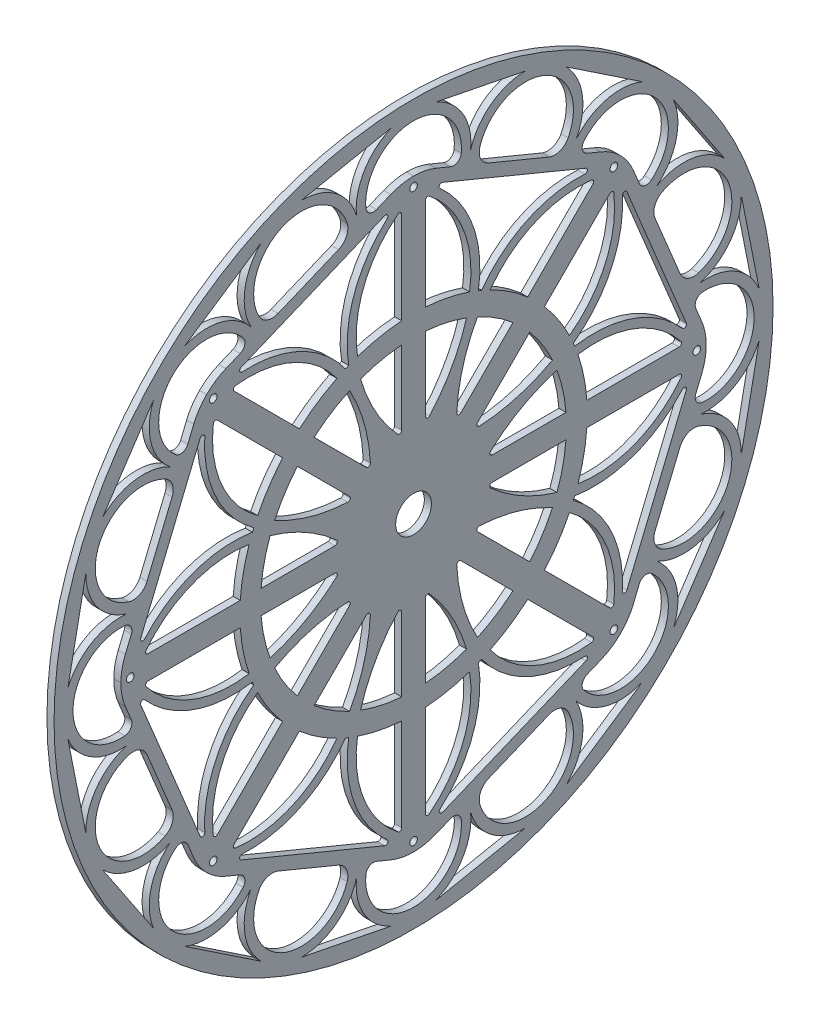
SolidWorks part; units mm, degrees
ref_plane "Front Plane" through (0, 0, 0) normal (1, 0, 0) x (0, 1, 0)
ref_plane "Top Plane" through (0, 0, 0) normal (0, 0, 1) x (0, 1, 0)
ref_plane "Right Plane" through (0, 0, 0) normal (0, 1, 0) x (-1, 0, 0)
sketch "Sketch1" plane through (0, 0, 0) normal (1, 0, 0) x (0, 1, 0)
  line L0 (0, 117.5907) -> (0, 0) construction
  line L1 (83.1492, 83.1492) -> (0, 117.5907) construction
  line L2 (0, 117.5907) -> (-83.1492, 83.1492) construction
  line L4 (-117.5907, 0) -> (-83.1492, -83.1492) construction
  line L5 (-83.1492, -83.1492) -> (0, -117.5907) construction
  line L6 (0, -117.5907) -> (83.1492, -83.1492) construction
  line L7 (83.1492, -83.1492) -> (117.5907, 0) construction
  line L8 (117.5907, 0) -> (83.1492, 83.1492) construction
  line L9 (-83.1492, 83.1492) -> (0, 0) construction
  line L10 (0, 0) -> (-117.5907, 0) construction
  line L11 (-117.5907, 0) -> (-118.1201, 0) construction
  line L12 (-123.5907, 0) -> (-123.5907, 5) construction
  line L14 (-36.2329, 29.1619) -> (-51.4539, 44.3828) construction
  line L15 (-90.9273, 83.8563) -> (-87.3918, 87.3918) construction
  line L16 (-87.3918, 87.3918) -> (-85.6448, 85.6448) construction
  line L18 (-121.1201, 0) -> (-123.5907, 0) construction
  line L19 (-123.5907, 5) -> (-90.9273, 83.8563) construction
  line L20 (-87.1005, 80.0294) -> (-118.1787, 5) construction
  line L21 (-55.2807, 48.2096) -> (-62.699, 30.3003) construction
  line L22 (-59.6103, 24.6914) -> (-36.2329, 29.1619) construction
  line L23 (-67.7667, 5) -> (-51.4539, 44.3828) construction
  line L24 (-59.6103, 24.6914) -> (-46.2411, 5) construction
  line L25 (0, 0) -> (-83.5235, 83.5235)
  line L26 (-55.2807, 48.2096) -> (-84.2721, 77.201) construction
  line L27 (-67.7667, 5) -> (-46.2411, 5) construction
  line L28 (-114.1787, 5) -> (-73.1787, 5) construction
  line L29 (-65.7604, 22.9093) -> (-73.1787, 5) construction
  line L30 (-85.6448, 85.6448) -> (-87.3918, 87.3918)
  line L31 (-83.1492, 83.1492) -> (-88.2348, 70.8713) construction
  line L32 (-87.3918, 87.3918) -> (-90.9273, 83.8563)
  line L33 (-90.9273, 83.8563) -> (-123.5907, 5)
  line L34 (-123.5907, 5) -> (-123.5907, 0)
  line L35 (-123.5907, 0) -> (-121.1201, 0)
  line L36 (-118.1201, 0) -> (0, 0)
  arc A0 (-108.6396, 0) -> (-76.8198, 76.8198) centre (0, 0) ccw construction
  arc A5 (-87.1005, 80.0294) -> (-64.2297, 26.6048) centre (-38.2585, 69.3307) ccw construction
  arc A6 (-114.1787, 5) -> (-65.7604, 22.9093) centre (-76.7606, -21.7561) cw construction
  arc A7 (-84.2721, 77.201) -> (-62.699, 30.3003) centre (-38.8941, 69.6618) ccw construction
  arc A8 (-118.1787, 5) -> (-64.2297, 26.6048) centre (-76.0771, -21.9713) cw construction
  arc A9 (-117.5907, 0) -> (-83.1492, 83.1492) centre (0, 0) ccw construction
  arc A12 (-85.6448, 85.6448) -> (-83.5235, 83.5235) centre (-84.5842, 84.5842) ccw
  arc A13 (-121.1201, 0) -> (-118.1201, 0) centre (-119.6201, 0) cw
  dimension "D1" = 6
  dimension "D8" = 50
  dimension "D9" = 4
  dimension "D12" = 46
  dimension "D13" = 4
  dimension "D4" = 1.5
  dimension "D11" = 1.5
  dimension "D2" = 90
  dimension "D3" = 5
  dimension "D5" = 5
  dimension "D7" = 5
  dimension "D10" = 45
extrude "Boss-Extrude3" add sketch "Sketch1" along normal blind 3
sketch "Sketch2" plane through (3, 0, 0) normal (1, 0, 0) x (0, 1, 0)
  line L0 (-84.2721, 77.201) -> (-55.2807, 48.2096)
  line L1 (-55.2807, 48.2096) -> (-62.699, 30.3003)
  line L2 (-65.7604, 22.9093) -> (-73.1787, 5)
  line L3 (-73.1787, 5) -> (-114.1787, 5)
  line L4 (-118.1787, 5) -> (-87.1005, 80.0294)
  arc A0 (-87.1005, 80.0294) -> (-64.2297, 26.6048) centre (-38.2585, 69.3307) ccw
  arc A1 (-62.699, 30.3003) -> (-84.2721, 77.201) centre (-38.8941, 69.6618) cw
  arc A2 (-64.2297, 26.6048) -> (-118.1787, 5) centre (-76.0771, -21.9713) ccw
  arc A3 (-65.7604, 22.9093) -> (-114.1787, 5) centre (-76.7606, -21.7561) ccw
extrude "Cut-Extrude5" cut sketch "Sketch2" against normal blind 3 contours A2 A0 L4 | A1 L1 L0 | L2 A3 L3 region at (3, -71.2812, 52.1242) region at (3, -87.2608, 13.5461) region at (3, -92.9106, 38.4849)
sketch "Sketch4" plane through (3, 0, 0) normal (1, 0, 0) x (0, 1, 0)
  line L0 (0, 0) -> (-83.5235, 83.5235) construction
  line L1 (-67.7667, 5) -> (-51.4539, 44.3828) construction
  line L2 (-118.1201, 0) -> (0, 0) construction
  line L3 (-58.6536, 27.0011) -> (-60.567, 22.3817) construction
  line L5 (-51.4539, 44.3828) -> (-25.2262, 18.1552)
  line L6 (-67.7667, 5) -> (-30.6753, 5)
  line L7 (-51.4539, 44.3828) -> (-58.6536, 27.0011)
  line L8 (-67.7667, 5) -> (-60.567, 22.3817)
  line L9 (-64.2297, 26.6048) -> (-59.6103, 24.6914) construction
  arc A0 (-18.3848, 18.3848) -> (-58.6536, 27.0011) centre (-24.2, 89.6145) cw construction
  arc A1 (-26, 0) -> (-60.567, 22.3817) centre (-80.479, -46.255) ccw construction
  arc A2 (-25.2262, 18.1552) -> (-58.6536, 27.0011) centre (-24.2, 89.6145) cw
  arc A3 (-60.567, 22.3817) -> (-30.6753, 5) centre (-80.479, -46.255) cw
  dimension "D1" = 26
  dimension "D2" = 26
  dimension "D3" = 5
  dimension "D4" = 5
extrude "Cut-Extrude6" cut sketch "Sketch4" against normal up to vertex (3 mm away) contours A2 L7 L5 | A3 L6 L8 up to point (0, -46.2411, 5)
fillet "Fillet3" radius 1 6 edges at (1.5, -118.1787, 5) (1.5, -87.1005, 80.0294) (1.5, -30.6753, 5) (1.5, -25.2262, 18.1552) (1.5, -114.1787, 5) (1.5, -84.2721, 77.201)
fillet "Fillet4" radius 25 2 edges at (1.5, -90.9273, 83.8563) (1.5, -123.5907, 5)
pattern_circular "CirPattern2" count 8 over 360 about axis through (3, 0, 0) along (-1, 0, 0) of "Boss-Extrude3", "Cut-Extrude5", "Cut-Extrude6", "Fillet3", "Fillet4"
sketch "Sketch5" plane through (3, 0, 0) normal (1, 0, 0) x (0, 0, -1)
  line L0 (0.0272, -123.5907) -> (0, -146.4823)
  line L1 (0, -146.4823) -> (0, -151.7532)
  line L2 (-87.411, -87.3726) -> (-103.6014, -103.5559)
  line L3 (-103.6014, -103.5559) -> (-107.3293, -107.2821)
  line L4 (-83.8563, -90.9273) -> (-5, -123.5907) construction
  line L5 (-62.7141, -99.6847) -> (-44.4281, -107.259) construction
  line L6 (-44.4281, -107.259) -> (-26.1422, -114.8333) construction
  line L7 (-87.411, -87.3726) -> (-62.7141, -99.6847) construction
  line L8 (-26.1422, -114.8333) -> (0.0272, -123.5907) construction
  line L9 (-103.6014, -103.5559) -> (-87.5988, -117.4032) construction
  line L10 (-21.1068, -144.9537) -> (0, -146.4823) construction
  circle A0 centre (0, 0) radius 151.7532 construction
  arc A1 (-107.3293, -107.2821) -> (0, -151.7532) centre (0, 0) ccw
  circle A2 centre (0, 0) radius 146.4823 construction
  arc A3 (-103.6014, -103.5559) -> (0, -146.4823) centre (0, 0) ccw
  arc A4 (-62.7141, -99.6847) -> (-103.6014, -103.5559) centre (-86.3933, -67.4466) cw
  arc A5 (-44.4281, -107.259) -> (-87.5988, -117.4032) centre (-73.2198, -81.6633) cw
  arc A6 (-26.1422, -114.8333) -> (0, -146.4823) centre (13.3992, -108.7933) ccw
  arc A7 (-44.4281, -107.259) -> (-21.1068, -144.9537) centre (-5.971, -109.5276) ccw
  dimension "D1" = 40
sketch "Sketch7" plane through (3, 0, 0) normal (1, 0, 0) x (0, 1, 0)
  line L0 (-90.9273, 83.8563) -> (-123.5907, 5) construction
  line L1 (-147.8187, 0) -> (-143.8187, 0)
  line L2 (-109.7756, 96.6635) -> (-131.3147, 64.4279)
  line L3 (-138.4109, 47.2961) -> (-145.9744, 9.2717)
  line L4 (-147.8187, 0) -> (-151.8187, 0)
  line L5 (-104.5236, 104.5236) -> (-107.352, 107.352)
  line L6 (-104.5236, 104.5236) -> (-101.6952, 101.6952)
  line L7 (-95.3376, 73.2089) -> (-101.9695, 57.198)
  line L8 (-119.1804, 15.6474) -> (-112.5485, 31.6582)
  circle A0 centre (0, 0) radius 123.5907 construction
  circle A1 centre (0, 0) radius 151.8187 construction
  arc A2 (-147.8187, 0) -> (-104.5236, 104.5236) centre (0, 0) ccw construction
  arc A3 (-68.6633, 102.7619) -> (-104.5236, 104.5236) centre (-87.3918, 87.3918) ccw construction
  arc A4 (-102.7619, 68.6633) -> (-131.3147, 64.4279) centre (-114.1829, 47.2961) ccw construction
  arc A5 (-121.2159, 24.1113) -> (-145.9744, 9.2717) centre (-123.5907, 0) ccw construction
  arc A6 (-102.7619, 68.6633) -> (-109.7756, 96.6635) centre (-87.3918, 87.3918) cw
  arc A7 (-102.7619, 68.6633) -> (-131.3147, 64.4279) centre (-114.1829, 47.2961) ccw
  arc A8 (-121.2159, 24.1113) -> (-145.9744, 9.2717) centre (-123.5907, 0) ccw
  arc A9 (-121.9353, 20.1602) -> (-143.8187, 0) centre (-123.5907, 0) ccw
  arc A10 (-100.4767, 71.9659) -> (-101.6952, 101.6952) centre (-87.3918, 87.3918) cw
  arc A11 (-104.9386, 65.2882) -> (-120.3685, 28.0371) centre (-114.1829, 47.2961) ccw
  arc A12 (-100.4767, 71.9659) -> (-95.3376, 73.2089) centre (-98.3603, 74.4609) ccw
  arc A13 (-104.9386, 65.2882) -> (-101.9695, 57.198) centre (-107.8449, 59.6317) cw
  arc A14 (-120.3685, 28.0371) -> (-112.5485, 31.6582) centre (-118.4238, 34.0919) ccw
  arc A15 (-121.9353, 20.1602) -> (-119.1804, 15.6474) centre (-122.2031, 16.8994) cw
  arc A16 (-107.352, 107.352) -> (-151.8187, 0) centre (0, 0) ccw
  arc A17 (-147.8187, 0) -> (-121.2159, -24.1113) centre (-123.5907, 0) ccw construction
  arc A18 (-138.4109, 47.2961) -> (-121.2159, 24.1113) centre (-114.1829, 47.2961) ccw construction
  arc A19 (-138.4109, 47.2961) -> (-121.2159, 24.1113) centre (-114.1829, 47.2961) ccw
  arc A20 (-109.7756, 96.6635) -> (-102.7619, 68.6633) centre (-87.3918, 87.3918) ccw construction
  dimension "D1" = 4
  dimension "D2" = 4
  dimension "D3" = 4
  dimension "D4" = 4
extrude "Boss-Extrude5" add sketch "Sketch7" against normal blind 3
sketch "Sketch8" plane through (3, 0, 0) normal (1, 0, 0) x (0, 0, -1)
  circle A0 centre (-84.5842, -84.5842) radius 1.6
  dimension "D1" = 3.2
extrude "Cut-Extrude7" cut sketch "Sketch8" against normal through all both and the other way through all
ref_axis "Axis3" through (-0.15, 0, 0) along (1, 0, 0)
pattern_circular "CirPattern4" count 8 over 360 about axis through (-0.15, 0, 0) along (1, 0, 0) of "Cut-Extrude7", "Boss-Extrude5"
sketch "Sketch9" plane through (0, 0, 0) normal (-1, 0, 0) x (0, 0, 1)
  circle A0 centre (0, 0) radius 64.5701
  circle A1 centre (0, 0) radius 73.3493
extrude "Boss-Extrude6" add sketch "Sketch9" against normal up to surface (3 mm away) up to face at (3, -119.6201, -1.6)
sketch "Sketch10" plane through (0, 0, 0) normal (-1, 0, 0) x (0, 0, 1)
  circle A0 centre (0, 0) radius 7.55
  dimension "D1" = 15.1
extrude "Cut-Extrude8" cut sketch "Sketch10" against normal blind 10
